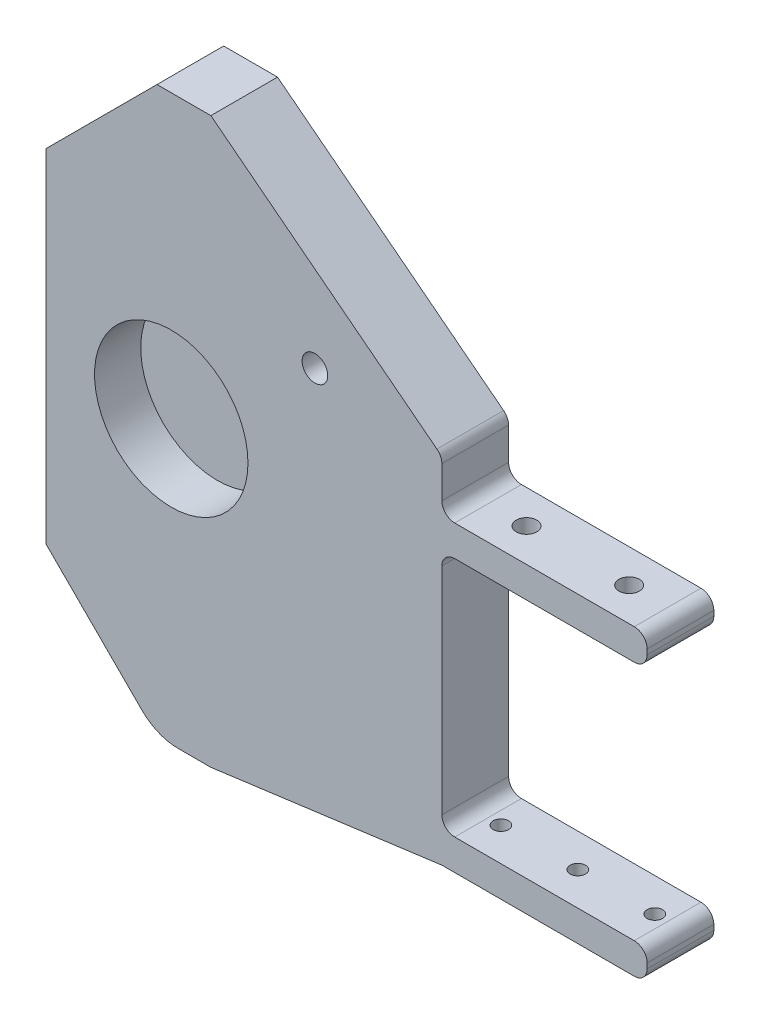
SolidWorks part; units mm, degrees
material "5052-H36"
ref_plane "Plano frontal" through (0, 0, 0) normal (0, 0, 1) x (1, 0, 0)
ref_plane "Plano superior" through (0, 0, 0) normal (0, 1, 0) x (1, 0, 0)
ref_plane "Plano direito" through (0, 0, 0) normal (1, 0, 0) x (0, 0, -1)
sketch "Esboço1" plane through (0, 0, 0) normal (0, 0, 1) x (1, 0, 0)
  line L0 (79.1281, 0) -> (0, 0) construction
  line L3 (4.9801, 55) -> (32.742, 55)
  line L6 (32.742, 55) -> (-22.7817, 55)
  line L12 (-22.7817, 55) -> (-44.3754, 33.4063)
  line L14 (-44.3754, -33.4063) -> (-22.7817, -55)
  line L15 (-22.7817, -55) -> (32.742, -55)
  line L18 (393.8557, 316.0739) -> (396.402, 318.6203) [skipped]
  line L19 (55, 501.996) -> (55, 520.8093) [skipped]
  line L20 (-316.0739, 393.8557) -> (-318.6203, 396.402) [skipped]
  line L21 (32.742, 55) -> (32.742, 10)
  line L22 (32.742, -49) -> (32.742, -55)
  line L23 (32.742, -49) -> (72.742, -49)
  line L25 (32.742, -43) -> (72.742, -43)
  line L26 (72.742, -49) -> (72.742, -43)
  line L27 (32.742, 4) -> (32.742, -43)
  line L28 (32.742, 4) -> (72.742, 4)
  line L30 (32.742, 10) -> (72.742, 10)
  line L31 (72.742, 4) -> (72.742, 10)
  line L32 (-44.3754, 33.4063) -> (-44.3754, -33.4063)
  line L34 (-55, 7.7563) -> (-55, -6.3461) [skipped]
  circle A0 centre (0, 0) radius 15 construction
  arc A3 (4.9801, 55) -> (0, -55.225) centre (0, 0) ccw construction
  point P14 (4.9801, 55)
  dimension "D1" = 30
  dimension "D5" = 110
  dimension "D6" = 40
  dimension "D7" = 6
  dimension "D8" = 6
  dimension "D9" = 45
extrude "Ressalto-extrusão1" add sketch "Esboço1" along normal mid plane 13 contours L14 L15 L3 L6 L12 A0 region at (-0.7875, -1.1016, 0)
sketch "Esboço2" plane through (0, 0, 6.5) normal (0, 0, 1) x (1, 0, 0)
  circle A1 centre (-20, 0) radius 14.95
  dimension "D1" = 29.9
  dimension "D2" = 20
extrude "Corte-extrusão1" cut sketch "Esboço2" against normal blind 9
sketch "Esboço3" plane through (0, 0, 6.5) normal (0, 0, 1) x (1, 0, 0)
  line L0 (-22.7817, -55) -> (32.742, -55) construction
  line L1 (-12.2817, -55) -> (32.742, -49)
  line L2 (32.742, -49) -> (32.742, -55)
  line L3 (32.742, -55) -> (-12.2817, -55)
  line L4 (-12.2817, -55) -> (-12.2817, 66.3095) construction
  line L6 (32.742, 10) -> (72.742, 10) construction
  line L11 (32.742, 55) -> (-12.2817, 55)
  line L12 (-12.2817, 55) -> (32.742, 20)
  line L13 (32.742, 20) -> (32.742, 55)
  circle A0 centre (8, 22.5) radius 2.5
  point P0 (-12.2817, -55)
  dimension "D2" = 5
  dimension "D1" = 10.5
  dimension "D3" = 22.5
  dimension "D4" = 28
  dimension "D5" = 10
extrude "Corte-extrusão2" cut sketch "Esboço3" against normal blind 13
fillet "Filete1" radius 10 1 edges at (-22.7817, -55, 0)
sketch "Esboço4" plane through (0, 0, -6.5) normal (0, 0, -1) x (-1, 0, 0)
  line L0 (44.3754, 33.4063) -> (44.3754, -33.4063) construction
  circle A0 centre (36.3754, 8.4063) radius 2
  circle A1 centre (12.9554, -16.5937) radius 2
  circle A2 centre (22.3754, -27.5937) radius 2
  dimension "D1" = 4
  dimension "D2" = 25
  dimension "D3" = 8
  dimension "D4" = 23.42
  dimension "D5" = 25
  dimension "D6" = 36
  dimension "D7" = 14
extrude "Corte-extrusão3" cut sketch "Esboço4" against normal blind 10
sketch "Esboço6" plane through (0, 10, 0) normal (0, 1, 0) x (1, 0, 0)
  line L0 (32.742, -6.5) -> (72.742, -6.5) construction
  circle A0 centre (42.742, -0.0016) radius 2
  circle A1 centre (62.742, -0.0016) radius 2
  circle A2 centre (42.742, -0.0016) radius 2 construction
  point P7 (62.742, -0.0016)
  dimension "D1" = 20
  dimension "D2" = 6.4984
extrude "Corte-extrusão4" cut sketch "Esboço6" against normal blind 10
sketch "Esboço7" plane through (0, -49, 0) normal (0, -1, 0) x (1, 0, 0)
  line L0 (32.742, -6.5) -> (72.742, -6.5) construction
  line L1 (37.742, 0) -> (67.742, 0) construction
  line L2 (72.742, 6.5) -> (72.742, -6.5) construction
  circle A0 centre (37.742, 0) radius 1.5
  circle A1 centre (52.742, 0) radius 1.5
  circle A2 centre (67.742, 0) radius 1.5
  dimension "D1" = 3
  dimension "D2" = 6.5
  dimension "D3" = 5
  dimension "D4" = 20
  dimension "D5" = 35
extrude "Corte-extrusão5" cut sketch "Esboço7" against normal blind 10
fillet "Filete2" radius 2.5 8 edges at (72.742, -49, 0) (72.742, -43, 0) (72.742, 4, 0) (72.742, 10, 0) (32.742, 20, 0) (32.742, -43, 0) (32.742, 10, 0) (32.742, 4, 0)
